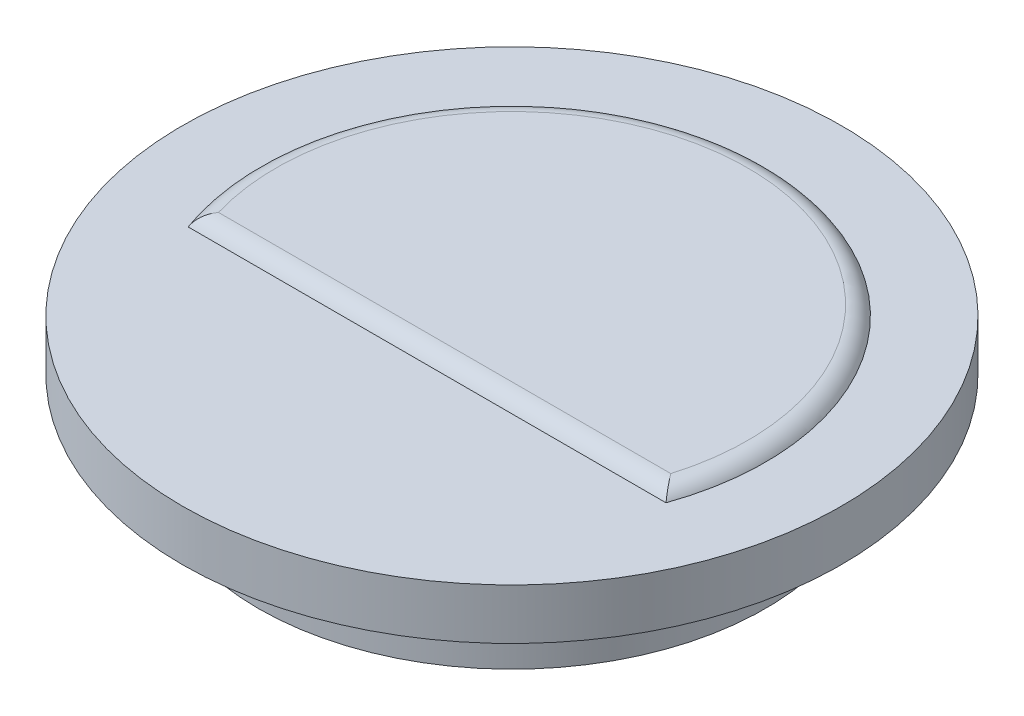
SolidWorks part; units mm, degrees
ref_plane "Front Plane" through (0, 0, 0) normal (0, 0, 1) x (1, 0, 0)
ref_plane "Top Plane" through (0, 0, 0) normal (0, 1, 0) x (1, 0, 0)
ref_plane "Right Plane" through (0, 0, 0) normal (1, 0, 0) x (0, 0, -1)
sketch "Sketch1" plane through (0, 0, 0) normal (0, 1, 0) x (1, 0, 0)
  line L0 (-47.1173, -16.732) -> (47.1173, -16.732)
  arc A0 (47.1173, -16.732) -> (-47.1173, -16.732) centre (0, 0) ccw
  circle A1 centre (0, 0) radius 65
  dimension "D1" = 100
  dimension "D2" = 130
extrude "Boss-Extrude1" add sketch "Sketch1" along normal blind 10
sketch "Sketch2" plane through (0, 10, 0) normal (0, 1, 0) x (1, 0, 0)
  line L0 (-47.1173, -16.732) -> (47.1173, -16.732) construction
  line L1 (-47.1173, -16.732) -> (47.1173, -16.732)
  arc A0 (-47.1173, -16.732) -> (47.1173, -16.732) centre (0, 0) cw
extrude "Boss-Extrude2" add sketch "Sketch2" along normal blind 2 separate body
fillet "Fillet1" radius 4 2 edges at (0, 12, 16.732) (0, 12, -50)
sketch "Sketch3" plane through (0, 0, 0) normal (0, -1, 0) x (1, 0, 0)
  circle A0 centre (0, 0) radius 50
extrude "Boss-Extrude8" add sketch "Sketch3" along normal blind 15 separate body
